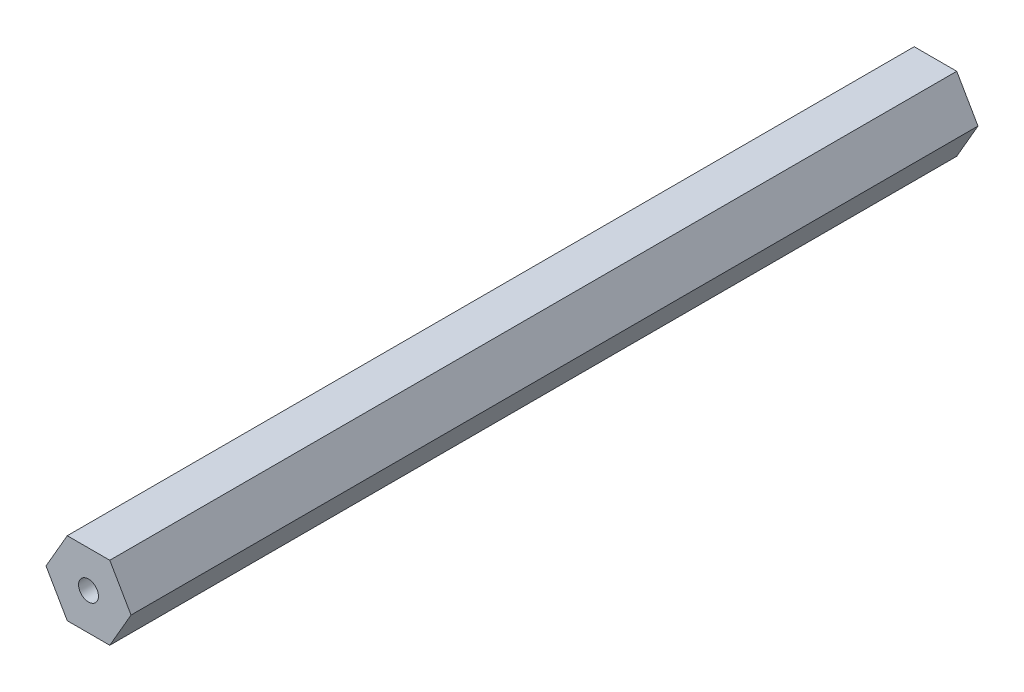
SolidWorks part; units mm, degrees
material "7075-T6 (SN)"
ref_plane "Front Plane" through (0, 0, 0) normal (0, 0, 1) x (1, 0, 0)
ref_plane "Top Plane" through (0, 0, 0) normal (0, 1, 0) x (1, 0, 0)
ref_plane "Right Plane" through (0, 0, 0) normal (1, 0, 0) x (0, 0, -1)
other "Configuration Table"
sketch "Sketch1" plane through (0, 0, 0) normal (0, 0, 1) x (1, 0, 0)
  line L1 (7.3323, 0) -> (3.6662, 6.35)
  line L2 (3.6662, 6.35) -> (-3.6662, 6.35)
  line L3 (-3.6662, 6.35) -> (-7.3323, 0)
  line L4 (-7.3323, 0) -> (-3.6662, -6.35)
  line L5 (-3.6662, -6.35) -> (3.6662, -6.35)
  line L6 (3.6662, -6.35) -> (7.3323, 0)
  circle A0 centre (0, 0) radius 6.35 construction
  circle A1 centre (0, 0) radius 1.7145
  dimension "D2" = 3.429
  dimension "D1" = 12.7
extrude "Boss-Extrude1" add sketch "Sketch1" along normal mid plane 146.05
fillet "Fillet1" [suppressed] radius 0.635
equation "\"length\"= 5.75"
equation "\"D1@Boss-Extrude1\"=\"length\""
